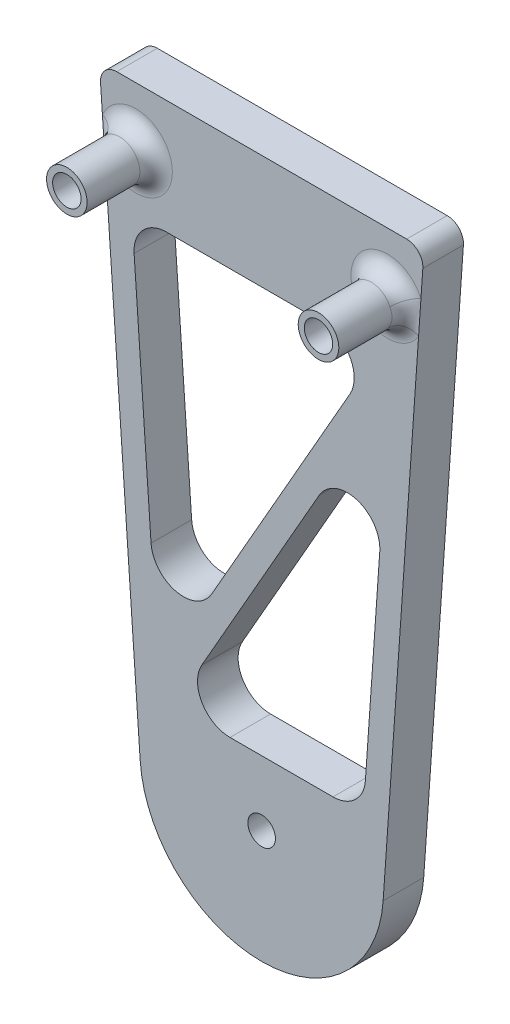
SolidWorks part; units mm, degrees
material "PLA"
ref_plane "Alzado" through (0, 0, 0) normal (0, 0, 1) x (1, 0, 0)
ref_plane "Planta" through (0, 0, 0) normal (0, 1, 0) x (1, 0, 0)
ref_plane "Vista lateral" through (0, 0, 0) normal (1, 0, 0) x (0, 0, -1)
sketch "Croquis1" plane through (0, 0, 0) normal (0, 0, 1) x (1, 0, 0)
  line L0 (0, 0) -> (0, -128.0927) construction
  line L1 (-20.0014, 0) -> (20.0014, 0)
  line L2 (20.0014, 0) -> (14.9635, -72.0463)
  line L3 (-20.0014, 0) -> (-14.9635, -72.0463)
  line L4 (-16.0119, -14.0463) -> (16.0119, -14.0463)
  line L5 (16.0119, -14.0463) -> (12.5155, -64.0463)
  line L6 (12.5155, -64.0463) -> (-12.5155, -64.0463)
  line L7 (-12.5155, -64.0463) -> (-16.0119, -14.0463)
  line L8 (-14.9635, -72.0463) -> (14.9635, -72.0463) construction
  line L9 (-12.7041, -61.35) -> (14.2849, -14.0463)
  line L10 (-12.5155, -64.0463) -> (16.0119, -14.0463) construction
  line L11 (-10.7886, -64.0463) -> (15.7707, -17.496)
  arc A0 (14.9635, -72.0463) -> (-14.9635, -72.0463) centre (0, -71) cw
  circle A1 centre (-15.5, -7.2763) radius 2.5
  circle A2 centre (15.5, -7.2763) radius 2.5
  circle A3 centre (-15.5, -7.2763) radius 1.75
  circle A4 centre (15.5, -7.2763) radius 1.75
  circle A5 centre (0, -72.0463) radius 1.7
  point P12 (0, -86)
  point P19 (0, -64.0463)
  dimension "D1" = 15
  dimension "D4" = 64.77
  dimension "D5" = 5
  dimension "D7" = 3.5
  dimension "D10" = 3.4
  dimension "D2" = 86
  dimension "D3" = 86
  dimension "D6" = 31
  dimension "D8" = 3
  dimension "D9" = 50
  dimension "D11" = 8
  dimension "D12" = 3
extrude "Saliente-Extruir1" add sketch "Croquis1" along normal mid plane 5 contours L0 L1 L3 A0 A1 | A1 | A2 | L1 L0 A0 L2 A2 | L6 L11 L5 L4 L9 L7 region at (0, -0.9485, 0) region at (1.6928, -39.1355, 0) region at (-17.9293, -7.2763, 0) region at (13.0707, -7.2763, 0)
extrude "Saliente-Extruir2" add sketch "Croquis1<3>" along normal blind 11 contours A1 | A2 | A3 | A4
sketch "Croquis1<3>" plane through (0, 0, 0) normal (0, 0, 1) x (1, 0, 0) same geometry as "Croquis1"
fillet "Redondeo1" radius 2 2 edges at (18, -7.2763, 2.5) (-13, -7.2763, 2.5)
fillet "Redondeo2" radius 2 2 edges at (20.0014, 0, 0) (-20.0014, 0, 0)
sketch "Croquis2" plane through (0, 0, -2.5) normal (0, 0, -1) x (-1, 0, 0)
  circle A12 centre (-15.5, -7.2763) radius 3
  circle A13 centre (15.5, -7.2763) radius 3
  dimension "D1" = 6
extrude "Cortar-Extruir1" cut sketch "Croquis2" against normal blind 2
fillet "Redondeo3" radius 4 6 edges at (-16.0119, -14.0463, 0) (12.5155, -64.0463, 0) (-10.7886, -64.0463, 0) (-12.7041, -61.35, 0) (14.2849, -14.0463, 0) (15.7707, -17.496, 0)
